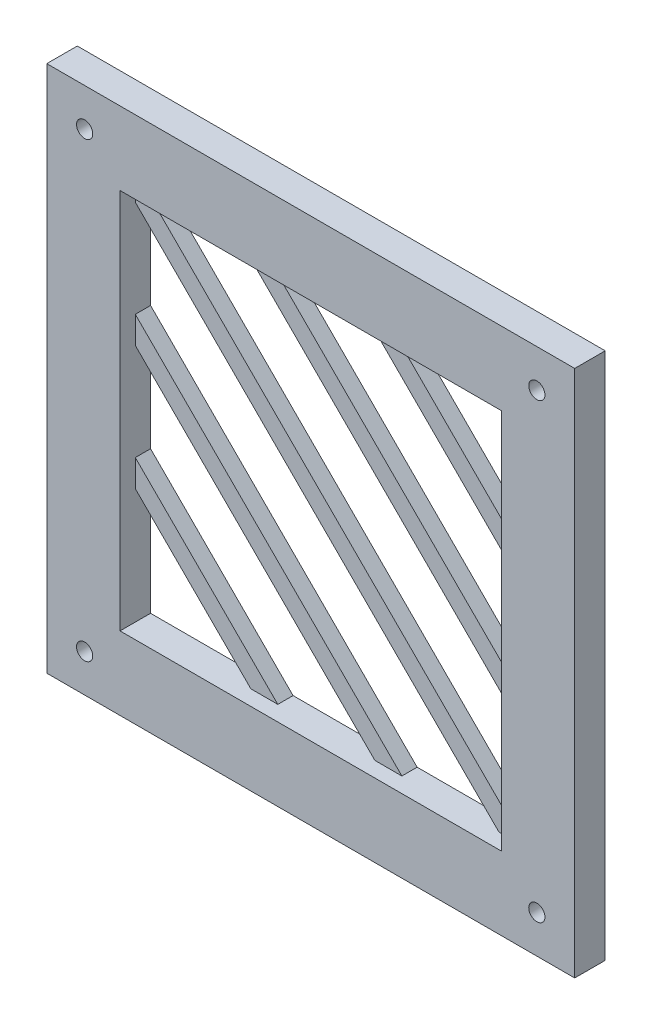
SolidWorks part; units mm, degrees
note: The reader was unsure of these and kept them because the rebuilt part matched: shared geometry of "Sketch2<3>".
ref_plane "Front Plane" through (0, 0, 0) normal (0, 0, 1) x (1, 0, 0)
ref_plane "Top Plane" through (0, 0, 0) normal (0, 1, 0) x (1, 0, 0)
ref_plane "Right Plane" through (0, 0, 0) normal (1, 0, 0) x (0, 0, -1)
sketch "Sketch1" plane through (0, 0, 0) normal (0, 0, 1) x (1, 0, 0)
  line L1 (-69.21, -69.21) -> (69.21, -69.21)
  line L2 (-69.21, -69.21) -> (-69.21, 69.21)
  line L3 (-69.21, 69.21) -> (69.21, 69.21)
  line L4 (69.21, -69.21) -> (69.21, 69.21)
  line L5 (-69.21, -69.21) -> (69.21, 69.21) construction
  line L6 (-69.21, 69.21) -> (69.21, -69.21) construction
  line L8 (76.131, 0) -> (-76.131, 0) construction
  circle A1 centre (-59.285, 59.285) radius 2.125
  circle A2 centre (59.285, -59.285) radius 2.125
  circle A3 centre (59.285, 59.285) radius 2.125
  circle A4 centre (-59.285, -59.285) radius 2.125
  point P0 (0, 0)
  dimension "D5" = 4.25
  dimension "D1" = 138.42
  dimension "D2" = 138.42
extrude "Boss-Extrude1" add sketch "Sketch1" along normal blind 8
sketch "Sketch2" plane through (0, 0, 8) normal (0, 0, 1) x (1, 0, 0)
  line L5 (-50, -50) -> (50, -50)
  line L6 (-50, -50) -> (-50, 50)
  line L7 (-50, 50) -> (50, 50)
  line L8 (50, -50) -> (50, 50)
  line L9 (-50, -50) -> (50, 50) construction
  line L10 (-50, 50) -> (50, -50) construction
  point P0 (0, 0)
  dimension "D1" = 100
  dimension "D2" = 100
extrude "Cut-Extrude10" cut sketch "Sketch2" against normal through all
ref_plane "Plane4" through (0, 0, 0) normal (0.7071, -0.7071, 0) x (-0.7071, -0.7071, 0)
sketch "Sketch12" plane through (0, 0, 0) normal (0.7071, -0.7071, 0) x (-0.7071, -0.7071, 0)
  line L0 (70.7107, -8) -> (-70.7107, -8) construction
  line L1 (-65.7107, -8) -> (-70.7107, -8)
  line L2 (-65.7107, -8) -> (-65.7107, 0)
  line L3 (-65.7107, 0) -> (-70.7107, 0)
  line L4 (-70.7107, -8) -> (-70.7107, 0)
  dimension "D1" = 5
extrude "Boss-Extrude12" add sketch "Sketch12" along normal up to next and the other way up to next
pattern_linear "LPattern2" count 6 spacing 23 along (-0.7071, -0.7071, 0) of "Boss-Extrude12"
extrude "Cut-Extrude13" cut sketch "Sketch2<3>" against normal blind 4
sketch "Sketch2<3>" plane through (0, 0, 8) normal (0, 0, 1) x (1, 0, 0) same geometry as "Sketch2"
